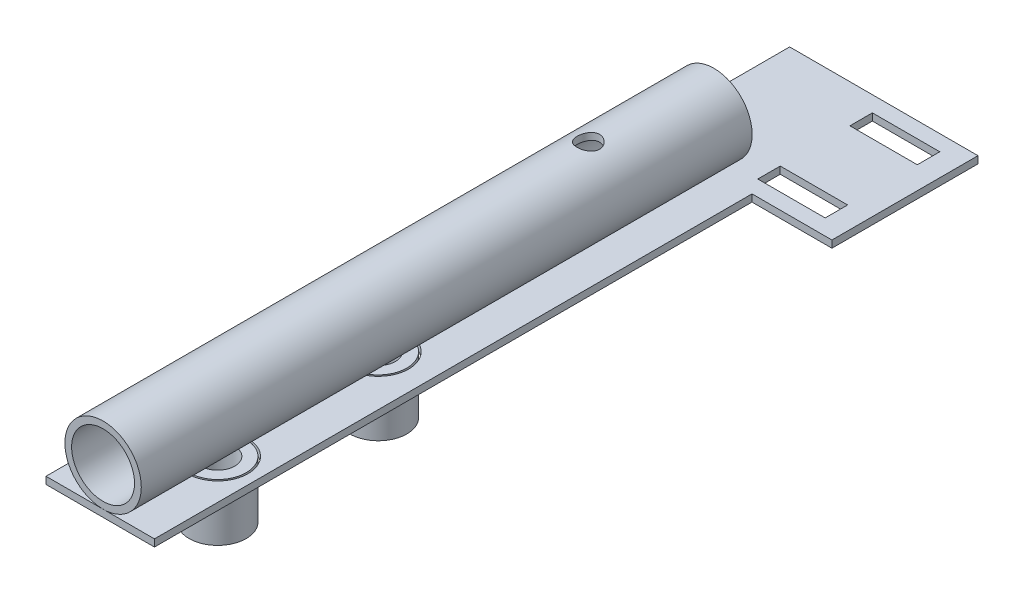
SolidWorks part; units mm, degrees
note: The reader was unsure of these and kept them because the rebuilt part matched: shared geometry of "Sketch6<5>".
ref_plane "Front Plane" through (0, 0, 0) normal (0, 0, 1) x (1, 0, 0)
ref_plane "Top Plane" through (0, 0, 0) normal (0, 1, 0) x (1, 0, 0)
ref_plane "Right Plane" through (0, 0, 0) normal (1, 0, 0) x (0, 0, -1)
sketch "Sketch1" plane through (0, 0, 0) normal (0, 1, 0) x (1, 0, 0)
  line L0 (-59.4061, 36.8) -> (49940.5939, 36.8) construction
  line L1 (22.86, -215.9) -> (-25.4, -215.9)
  line L2 (22.86, -215.9) -> (22.86, 50)
  line L3 (22.86, 115) -> (-25.4, 115)
  line L4 (-25.4, -215.9) -> (-25.4, 115)
  line L5 (22.86, -215.9) -> (-25.4, 115) construction
  line L6 (22.86, 115) -> (-25.4, -215.9) construction
  line L11 (22.86, 50) -> (22.86, 115) construction
  line L12 (22.86, 115) -> (58.42, 115)
  line L17 (22.86, 115) -> (22.86, 50) construction
  line L18 (22.86, 50) -> (58.42, 50)
  line L19 (58.42, 115) -> (58.42, 50)
  circle A0 centre (0, 0) radius 5
  point P4 (-1.27, -50.45)
  dimension "D1" = 10
  dimension "D2" = 22.86
  dimension "D3" = 115
  dimension "D4" = 36.8
  dimension "D5" = 48.26
  dimension "D6" = 65
  dimension "D7" = 35.56
  dimension "D8" = 58.42
  dimension "D11" = 215.9
base flange "Base-Flange1" sketch "Sketch1" thickness 3.175 reverse thickness direction no parameters "D1"=10
sketch "Sketch7" plane through (0, 0, 0) normal (0, 0, 1) x (1, 0, 0)
  line L0 (-25.4, -3.175) -> (-25.4, 0) construction
  line L1 (3.5097, 0) -> (-3.5097, 0) construction
  line L2 (0, 0) -> (0, 17) construction
  line L4 (-25.4, 0) -> (22.86, 0) construction
  circle A0 centre (0, 17) radius 17
  circle A1 centre (0, 17) radius 14
  dimension "D1" = 34
  dimension "D2" = 28
  dimension "D3" = 25.4
  dimension "D4" = 22.86
extrude "Boss-Extrude2" add sketch "Sketch7" along normal up to surface (215.9 mm away) and the other way blind 55.92 separate body up to face at (-1.27, -1.5875, 215.9)
sketch "Sketch8" plane through (0, 0, 0) normal (0, 1, 0) x (1, 0, 0)
  circle A0 centre (0, 0) radius 5 construction
  circle A1 centre (0, 0) radius 5
extrude "Cut-Extrude1" cut sketch "Sketch8" against normal through all both and the other way through all
sketch "Sketch9" plane through (0, -3.175, 0) normal (0, -1, 0) x (1, 0, 0)
  line L0 (58.42, -50) -> (58.42, -115) construction
  line L1 (18.42, -108) -> (48.42, -108)
  line L2 (18.42, -108) -> (18.42, -98)
  line L3 (18.42, -98) -> (48.42, -98)
  line L4 (48.42, -108) -> (48.42, -98)
  line L5 (18.42, -108) -> (48.42, -98) construction
  line L6 (18.42, -98) -> (48.42, -108) construction
  line L7 (18.42, -67) -> (48.42, -67)
  line L8 (18.42, -67) -> (18.42, -57)
  line L9 (18.42, -57) -> (48.42, -57)
  line L10 (48.42, -67) -> (48.42, -57)
  line L11 (18.42, -67) -> (48.42, -57) construction
  line L12 (18.42, -57) -> (48.42, -67) construction
  line L13 (58.42, -50) -> (58.42, -115) construction
  line L14 (58.42, -82.5) -> (16.0948, -82.5) construction
  line L15 (48.42, -98) -> (48.42, -82.5) construction
  line L16 (48.42, -82.5) -> (48.42, -67) construction
  point P4 (33.42, -103)
  point P9 (33.42, -62)
  dimension "D1" = 31
  dimension "D2" = 30
  dimension "D3" = 10
  dimension "D4" = 10
extrude "Cut-Extrude2" cut sketch "Sketch9" against normal up to next (3.175 mm away)
sketch "Sketch6" plane through (0, -3.175, 0) normal (0, 1, 0) x (1, 0, 0)
  line L0 (5.08, -170) -> (0.508, -93.9373) construction
  line L1 (2.794, -131.9686) -> (11.8767, -131.4227) construction
  line L2 (-25.4, -215.9) -> (22.86, -215.9) construction
  line L4 (22.86, -215.9) -> (22.86, 50) construction
  line L5 (-25.4, 115) -> (-25.4, -215.9) construction
  circle A0 centre (5.08, -170) radius 7.62
  circle A1 centre (5.08, -170) radius 12.7
  circle A4 centre (0.508, -93.9373) radius 7.62
  circle A5 centre (0.508, -93.9373) radius 12.7
  circle A6 centre (5.08, -170) radius 13.4937
  circle A7 centre (0.508, -93.9373) radius 13.4938
  dimension "D3" = 25.4
  dimension "D4" = 5.08
  dimension "D7" = 15.24
  dimension "D9" = 3.44
  dimension "D1" = 25.908
  dimension "D2" = 170
  dimension "D5" = 76.0627
  dimension "D6" = 45.9
  dimension "D10" = 121.9627
  dimension "D11" = 30.48
  dimension "D8" = 0.7937
extrude "Cut-Extrude4" cut sketch "Sketch6" along normal up to next (3.175 mm away) contours A7 | A6
extrude "Boss-Extrude3" add sketch "Sketch6<5>" along normal up to surface (3.175 mm away) and the other way blind 22.225 separate body contours A4 | A5 | A0 | A1 up to face at (18.6267, 0, 16.9667)
sketch "Sketch6<5>" plane through (0, -3.175, 0) normal (0, 1, 0) x (1, 0, 0) same geometry as "Sketch6"
sketch "Bend-Lines1" [suppressed] plane through (0, 0, 0) normal (0, 1, 0) x (1, 0, 0)
sketch "Bounding-Box1" [suppressed] plane through (0, 0, 0) normal (0, 1, 0) x (1, 0, 0)
sheet metal parameters "Sheet-Metal1" thickness 3.175 parameters "D1"=10
flat pattern "Flat-Pattern1" [suppressed]
sketch "Bend-Lines2" plane through (0, 0, 0) normal (0, 1, 0) x (1, 0, 0)
sketch3d "Bounding-Box2" [suppressed]
  line L0 (-25.4, -215.9, 0) -> (-25.4, 115, 0) construction
  line L1 (58.42, -215.9, 0) -> (58.42, 115, 0) construction
  line L2 (-25.4, -215.9, 0) -> (58.42, -215.9, 0) construction
  line L3 (-25.4, 115, 0) -> (58.42, 115, 0) construction
sheet metal parameters "Sheet-Metal6" thickness 3.175 parameters "D1"=10
flat pattern "Flat-Pattern1" [suppressed]
sketch "Bend-Lines2" plane through (0, 0, 0) normal (0, 1, 0) x (1, 0, 0)
sketch3d "Bounding-Box2" [suppressed]
  line L0 (-25.4, -215.9, 0) -> (-25.4, 115, 0) construction
  line L1 (58.42, -215.9, 0) -> (58.42, 115, 0) construction
  line L2 (-25.4, -215.9, 0) -> (58.42, -215.9, 0) construction
  line L3 (-25.4, 115, 0) -> (58.42, 115, 0) construction
sketch "Sketch9-1" plane through (0, -3.175, 0) normal (0, -1, 0) x (1, 0, 0)
  line L1 (18.42, -108) -> (48.42, -108)
  line L2 (18.42, -108) -> (18.42, -98)
  line L3 (18.42, -98) -> (48.42, -98)
  line L4 (48.42, -108) -> (48.42, -98)
  line L5 (18.42, -108) -> (48.42, -98) construction
  line L6 (18.42, -98) -> (48.42, -108) construction
  line L7 (18.42, -67) -> (48.42, -67)
  line L8 (18.42, -67) -> (18.42, -57)
  line L9 (18.42, -57) -> (48.42, -57)
  line L10 (48.42, -67) -> (48.42, -57)
  line L11 (18.42, -67) -> (48.42, -57) construction
  line L12 (18.42, -57) -> (48.42, -67) construction
  line L13 (58.42, -50) -> (58.42, -115) construction
  line L14 (58.42, -82.5) -> (16.0948, -82.5) construction
  line L15 (48.42, -98) -> (48.42, -82.5) construction
  line L16 (48.42, -82.5) -> (48.42, -67) construction
  point P4 (33.42, -103)
  point P9 (33.42, -62)
  dimension "D1" = 31
  dimension "D2" = 30
  dimension "D3" = 10
  dimension "D4" = 10
sketch "Sketch6-1" [suppressed] plane through (0, -3.175, 0) normal (0, 1, 0) x (1, 0, 0)
  line L0 (-3.048, -170) -> (-7.62, -106.6648) construction
  line L1 (-5.334, -138.3324) -> (12.21, -137.0659) construction
  line L3 (-25.4, 115) -> (-25.4, -215.9) construction
  circle A0 centre (-3.048, -170) radius 10.16
  circle A1 centre (-3.048, -170) radius 15.24
  circle A4 centre (-7.62, -106.6648) radius 10.16
  circle A5 centre (-7.62, -106.6648) radius 15.24
  dimension "D3" = 30.48
  dimension "D4" = 5.08
  dimension "D7" = 20.32
  dimension "D1" = 22.352
  dimension "D2" = 170
  dimension "D5" = 63.5
  dimension "D6" = 17.78
sheet metal parameters "Sheet-Metal9" thickness 3.175 parameters "D1"=10
flat pattern "Flat-Pattern1" [suppressed]
sketch "Bend-Lines2" plane through (0, 0, 0) normal (0, 1, 0) x (1, 0, 0)
sketch3d "Bounding-Box2" [suppressed]
  line L0 (-25.4, -215.9, 0) -> (-25.4, 115, 0) construction
  line L1 (58.42, -215.9, 0) -> (58.42, 115, 0) construction
  line L2 (-25.4, -215.9, 0) -> (58.42, -215.9, 0) construction
  line L3 (-25.4, 115, 0) -> (58.42, 115, 0) construction
sketch "Sketch9-1" plane through (0, -3.175, 0) normal (0, -1, 0) x (1, 0, 0)
  line L1 (18.42, -108) -> (48.42, -108)
  line L2 (18.42, -108) -> (18.42, -98)
  line L3 (18.42, -98) -> (48.42, -98)
  line L4 (48.42, -108) -> (48.42, -98)
  line L5 (18.42, -108) -> (48.42, -98) construction
  line L6 (18.42, -98) -> (48.42, -108) construction
  line L7 (18.42, -67) -> (48.42, -67)
  line L8 (18.42, -67) -> (18.42, -57)
  line L9 (18.42, -57) -> (48.42, -57)
  line L10 (48.42, -67) -> (48.42, -57)
  line L11 (18.42, -67) -> (48.42, -57) construction
  line L12 (18.42, -57) -> (48.42, -67) construction
  line L13 (58.42, -50) -> (58.42, -115) construction
  line L14 (58.42, -82.5) -> (16.0948, -82.5) construction
  line L15 (48.42, -98) -> (48.42, -82.5) construction
  line L16 (48.42, -82.5) -> (48.42, -67) construction
  point P4 (33.42, -103)
  point P9 (33.42, -62)
  dimension "D1" = 31
  dimension "D2" = 30
  dimension "D3" = 10
  dimension "D4" = 10
sketch "Sketch6-1" [suppressed] plane through (0, -3.175, 0) normal (0, 1, 0) x (1, 0, 0)
  line L0 (5.08, -170) -> (0.508, -93.9373) construction
  line L1 (2.794, -131.9686) -> (11.8767, -131.4227) construction
  line L2 (-25.4, -215.9) -> (22.86, -215.9) construction
  line L4 (22.86, -215.9) -> (22.86, 50) construction
  line L5 (-25.4, 115) -> (-25.4, -215.9) construction
  circle A0 centre (5.08, -170) radius 7.62
  circle A1 centre (5.08, -170) radius 12.7
  circle A4 centre (0.508, -93.9373) radius 7.62
  circle A5 centre (0.508, -93.9373) radius 12.7
  circle A6 centre (5.08, -170) radius 13.4937
  circle A7 centre (0.508, -93.9373) radius 13.4938
  dimension "D3" = 25.4
  dimension "D4" = 5.08
  dimension "D7" = 15.24
  dimension "D9" = 3.44
  dimension "D1" = 25.908
  dimension "D2" = 170
  dimension "D5" = 76.0627
  dimension "D6" = 45.9
  dimension "D10" = 121.9627
  dimension "D11" = 30.48
